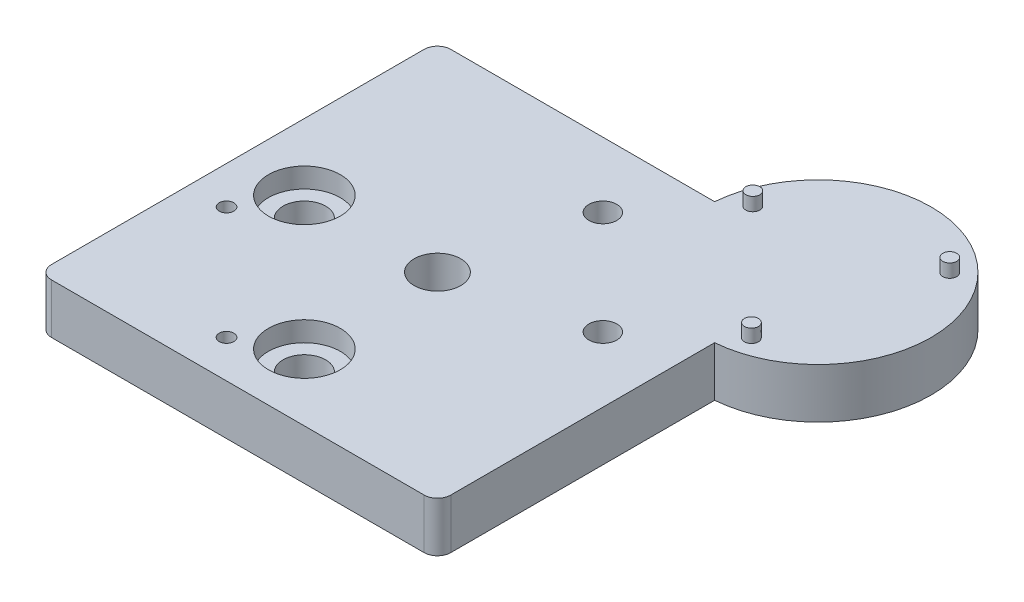
SolidWorks part; units mm, degrees
ref_plane "Front Plane" through (0, 0, 0) normal (0, 0, 1) x (1, 0, 0)
ref_plane "Top Plane" through (0, 0, 0) normal (0, 1, 0) x (1, 0, 0)
ref_plane "Right Plane" through (0, 0, 0) normal (1, 0, 0) x (0, 0, -1)
sketch "Sketch1" plane through (0, 0, 0) normal (0, 1, 0) x (1, 0, 0)
  line L0 (-38.1, -38.1) -> (56.218, 56.218) construction
  line L1 (-38.1, 38.1) -> (38.1, 38.1)
  line L2 (-38.1, 38.1) -> (-38.1, -38.1)
  line L3 (-38.1, -38.1) -> (38.1, -38.1)
  line L4 (38.1, 38.1) -> (38.1, -38.1)
  line L5 (-38.1, 38.1) -> (38.1, -38.1) construction
  line L6 (-38.1, -38.1) -> (38.1, 38.1) construction
  point P0 (0, 0)
  point P6 (0, 0)
  dimension "D1" = 76.2
extrude "Boss-Extrude1" add sketch "Sketch1" along normal blind 9.525
sketch "Sketch6" plane through (0, 0, 0) normal (0, 1, 0) x (1, 0, 0)
  line L0 (38.1, 38.1) -> (-38.1, 38.1) construction
  line L1 (-38.1, 38.1) -> (-38.1, -38.1) construction
  line L2 (38.1, -38.1) -> (38.1, 38.1) construction
  line L3 (-38.1, -38.1) -> (38.1, -38.1) construction
  circle A0 centre (-28.575, 28.575) radius 3.81
  circle A1 centre (28.575, -28.575) radius 3.81
  dimension "D2" = 7.62
  dimension "D1" = 9.525
  dimension "D3" = 9.525
  dimension "D4" = 9.525
  dimension "D5" = 9.525
extrude "Cut-Extrude2" cut sketch "Sketch6" along direction (0, 1, 0) on the side of the normal blind 2.54 draft 30
sketch "Sketch7" plane through (0, 0, 0) normal (0, 1, 0) x (1, 0, 0)
  line L2 (-38.1, 38.1) -> (-38.1, -38.1) construction
  line L3 (-38.1, -38.1) -> (38.1, -38.1) construction
  circle A0 centre (-27.94, -27.94) radius 4.445
  dimension "D3" = 8.89
  dimension "D2" = 10.16
  dimension "D1" = 10.16
sketch "Sketch12" plane through (0, 9.525, 0) normal (0, 1, 0) x (1, 0, 0)
  line L2 (-38.1, -38.1) -> (38.1, -38.1) construction
  line L3 (-38.1, 38.1) -> (-38.1, -38.1) construction
  circle A0 centre (-25.4, 0) radius 4.064
  circle A1 centre (0, -25.4) radius 4.064
  dimension "D2" = 12.7
  dimension "D3" = 8.128
  dimension "D4" = 38.1
  dimension "D5" = 12.7
  dimension "D1" = 38.1
extrude "Cut-Extrude4" cut sketch "Sketch12" against normal up to next
sketch "Sketch13" plane through (0, 9.525, 0) normal (0, -1, 0) x (1, 0, 0)
  circle A0 centre (0, 25.4) radius 4.064 construction
  circle A1 centre (-25.4, 0) radius 4.064 construction
  circle A6 centre (-25.4, 0) radius 6.858
  circle A9 centre (0, 25.4) radius 6.858
  point P0 (0, 0)
  dimension "D1" = 13.716
  dimension "D2" = 13.716
extrude "Cut-Extrude7" cut sketch "Sketch13" along normal blind 3.81
extrude "Cut-Extrude8" cut sketch "Sketch7" along normal blind 3.81 draft 45
ref_axis "Axis1" through (0, -9.5852, 25.4) along (0, 1, 0)
ref_axis "Axis2" through (-25.4, -15.4165, 0) along (0, 1, 0)
sketch "Sketch15" plane through (0, 9.525, 0) normal (0, 1, 0) x (1, 0, 0)
  circle A4 centre (0, 0) radius 4.445
  dimension "D1" = 8.89
extrude "Cut-Extrude9" cut sketch "Sketch15" against normal up to next
fillet "Fillet1" radius 2.54 4 edges at (38.1, 4.7625, -38.1) (38.1, 4.7625, 38.1) (-38.1, 4.7625, 38.1) (-38.1, 4.7625, -38.1)
sketch "Sketch17" plane through (0, 9.525, 0) normal (0, 1, 0) x (1, 0, 0)
  line L0 (38.1, -35.56) -> (38.1, 35.56) construction
  line L1 (35.56, 38.1) -> (-35.56, 38.1) construction
  circle A0 centre (36.3113, 36.3113) radius 21.59
  point P5 (36.3113, 36.3113)
  dimension "D1" = 43.18
  dimension "D2" = 1.7887
  dimension "D3" = 1.7887
extrude "Boss-Extrude2" add sketch "Sketch17" against normal up to surface (9.525 mm away) up to face at (0, 0, 4.445)
sketch "Sketch18" plane through (0, 9.525, 0) normal (0, 1, 0) x (1, 0, 0)
  line L0 (-38.1, 35.56) -> (-38.1, -35.56) construction
  circle A0 centre (19.1663, 41.0207) radius 1.3335
  circle A2 centre (48.9622, 48.8046) radius 1.3335
  circle A3 centre (40.8053, 19.1086) radius 1.3335
  point P10 (36.3113, 36.3113)
  dimension "D1" = 2.667
  dimension "D2" = 17.78
  dimension "D4" = 57.2663
  dimension "D5" = 74.4113
  dimension "D6" = 78.9053
  dimension "D3" = 3
extrude "Boss-Extrude3" add sketch "Sketch18" along normal blind 2.54
sketch "Sketch23" plane through (0, 9.525, 0) normal (0, 1, 0) x (1, 0, 0)
  line L0 (-38.1, -38.1) -> (56.218, 56.218) construction
  circle A0 centre (-9.352, -30.9046) radius 1.397
  circle A1 centre (-30.9046, -9.352) radius 1.397
  circle A2 centre (5.9033, 25.6598) radius 2.667
  circle A3 centre (25.6598, 5.9033) radius 2.667
  point P1 (0, 0)
  point P8 (0, 0)
  point P10 (0, 0)
  point P11 (0, 0)
  point P12 (0, 0)
  dimension "D1" = 5.334
  dimension "D2" = 5.334
  dimension "D3" = 2.794
  dimension "D4" = 2.794
  dimension "D5" = 50.8
  dimension "D6" = 27.94
  dimension "D7" = 15.24
  dimension "D8" = 15.24
  dimension "D9" = 13.97
  dimension "D10" = 13.97
  dimension "D11" = 50.8
extrude "Cut-Extrude11" cut sketch "Sketch23" against normal up to surface (9.525 mm away) up to face at (0.4799, 0, -0.4799)
